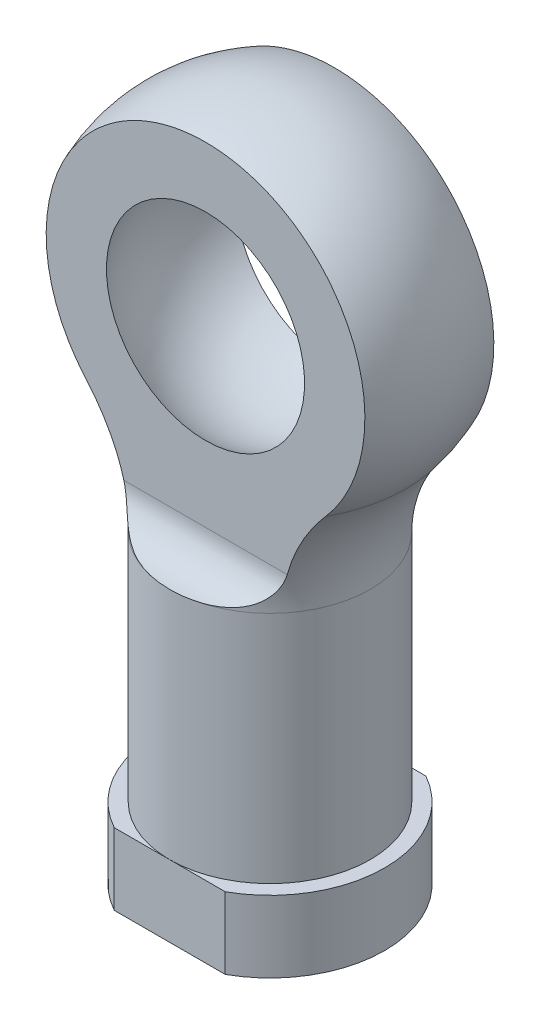
SolidWorks part; units mm, degrees
ref_plane "Front" through (0, 0, 0) normal (0, 0, 1) x (1, 0, 0)
ref_plane "Top" through (0, 0, 0) normal (0, 1, 0) x (1, 0, 0)
ref_plane "Right" through (0, 0, 0) normal (1, 0, 0) x (0, 0, -1)
sketch "Sketch1" plane through (0, 0, 0) normal (0, 0, 1) x (1, 0, 0)
  line L0 (0, 0) -> (0, -17) construction
  line L1 (0, -17) -> (4, -17) construction
  line L2 (4, -17) -> (4, 0) construction
  line L3 (4, 0) -> (0, 0) construction
  line L5 (0, 31) -> (0, 0) construction
  line L6 (0, 31) -> (12, 31) construction
  line L7 (12, 31) -> (12, 19) construction
  line L8 (-4, -17) -> (-4, 0) construction
  line L9 (7, 4.3371) -> (7, -12)
  line L10 (7, -12) -> (8, -12)
  line L11 (8, -12) -> (8, -17)
  line L12 (8, -17) -> (0, -17)
  line L13 (0, -17) -> (0, 4.3371)
  line L14 (0, 4.3371) -> (7, 4.3371)
  line L15 (0, 7) -> (7.2992, 7) construction
  arc A0 (9.5, 11.6686) -> (0, 31) centre (0, 19) ccw construction
  circle A1 centre (0, 19) radius 4 construction
  circle A2 centre (0, 19) radius 7.9 construction
  circle A3 centre (0, 19) radius 8.25 construction
  arc A4 (9.5, 11.6686) -> (0, 7) centre (0, 19) cw construction
  arc A5 (9.5, 11.6686) -> (7, 4.3371) centre (19, 4.3371) ccw construction
  dimension "D1" = 16.5
  dimension "A" = 8
  dimension "Ball Dia" = 15.8
  dimension "B" = 24
  dimension "D" = 36
  dimension "E" = 17
  dimension "Thread Dia" = 8
  dimension "Wrench Flats" = 14
  dimension "Base Dia" = 16
  dimension "Base Height" = 5
revolve "Revolve1" add sketch "Sketch1" angle 360 about L5
sketch "Sketch12" plane through (0, 0, 0) normal (0, 0, 1) x (1, 0, 0)
  line L1 (0, 0) -> (0, 4.3371) construction
  line L2 (8, -17) -> (0, -17) construction
  line L3 (4, -17) -> (4, 0) construction
  line L4 (4, 0) -> (0, 0) construction
  line L5 (4, -17) -> (0, -17)
  line L6 (4, -17) -> (4, 0)
  line L7 (4, 0) -> (0, 0)
  line L8 (0, -17) -> (0, 4.3371) construction
  line L9 (0, -17) -> (0, 0)
sketch "Sketch14" plane through (0, -12, 0) normal (0, 1, 0) x (-1, 0, 0)
  line L0 (-7, 0) -> (7, 0) construction
  line L1 (7, 7) -> (-7, 7)
  line L2 (7, 7) -> (7, -7) construction
  line L3 (7, -7) -> (-7, -7)
  line L4 (-7, 7) -> (-7, -7) construction
  line L5 (-7, -7) -> (-7, -8)
  line L6 (-7, -8) -> (7, -8)
  line L7 (7, -8) -> (7, -7)
  line L8 (7, 7) -> (7, 8)
  line L9 (7, 8) -> (-7, 8)
  line L10 (-7, 8) -> (-7, 7)
  circle A0 centre (0, 0) radius 8 construction
extrude "Cut-Extrude5" cut sketch "Sketch14" against normal through all and the other way through all
sketch "Sketch4" plane through (0, 0, 0) normal (0, 0, 1) x (1, 0, 0)
  line L0 (0, 10.75) -> (0, 4.3371)
  line L3 (7, 4.3371) -> (0, 4.3371)
  line L4 (0, 31) -> (0, 0) construction
  line L5 (0, 31) -> (0, 27.25)
  line L6 (0, 31) -> (0, 33.54) construction
  arc A0 (9.5, 11.6686) -> (0, 31) centre (0, 19) ccw construction
  arc A1 (9.5, 11.6686) -> (0, 31) centre (0, 19) ccw
  arc A2 (9.5, 11.6686) -> (7, 4.3371) centre (19, 4.3371) ccw construction
  arc A3 (9.5, 11.6686) -> (7, 4.3371) centre (19, 4.3371) ccw
  circle A4 centre (0, 19) radius 8.25 construction
  arc A5 (0, 10.75) -> (0, 27.25) centre (0, 19) ccw
  dimension "D1" = 2.54
revolve "Revolve2" add sketch "Sketch4" angle 360 about L6
sketch "Sketch5" plane through (0, 0, 0) normal (1, 0, 0) x (0, 0, -1)
  line L0 (4.5, 31) -> (12, 31)
  line L1 (-4.5, 31) -> (4.5, 31) construction
  line L2 (-4.5, 31) -> (-4.5, 4.3371)
  line L3 (-4.5, 4.3371) -> (4.5, 4.3371) construction
  line L4 (4.5, 31) -> (4.5, 4.3371)
  line L5 (12, 31) -> (12, 4.3371)
  line L6 (12, 4.3371) -> (4.5, 4.3371)
  line L7 (-4.5, 4.3371) -> (-12, 4.3371)
  line L8 (-12, 4.3371) -> (-12, 31)
  line L9 (-12, 31) -> (-4.5, 31)
  line L11 (-7, 4.3371) -> (-7, -12) construction
  arc A0 (9.5, 11.6686) -> (-9.5, 11.6686) centre (0, 19) ccw construction
  dimension "D1" = 2.5
  dimension "F" = 9
extrude "Cut-Extrude1" cut sketch "Sketch5" against normal through all and the other way through all
revolve "Cut-Revolve1" cut sketch "Sketch12" angle 360 about L1
fillet "Fillet1" radius 2.5 2 edges at (0, 4.3371, 4.5) (0, 4.3371, -4.5)
